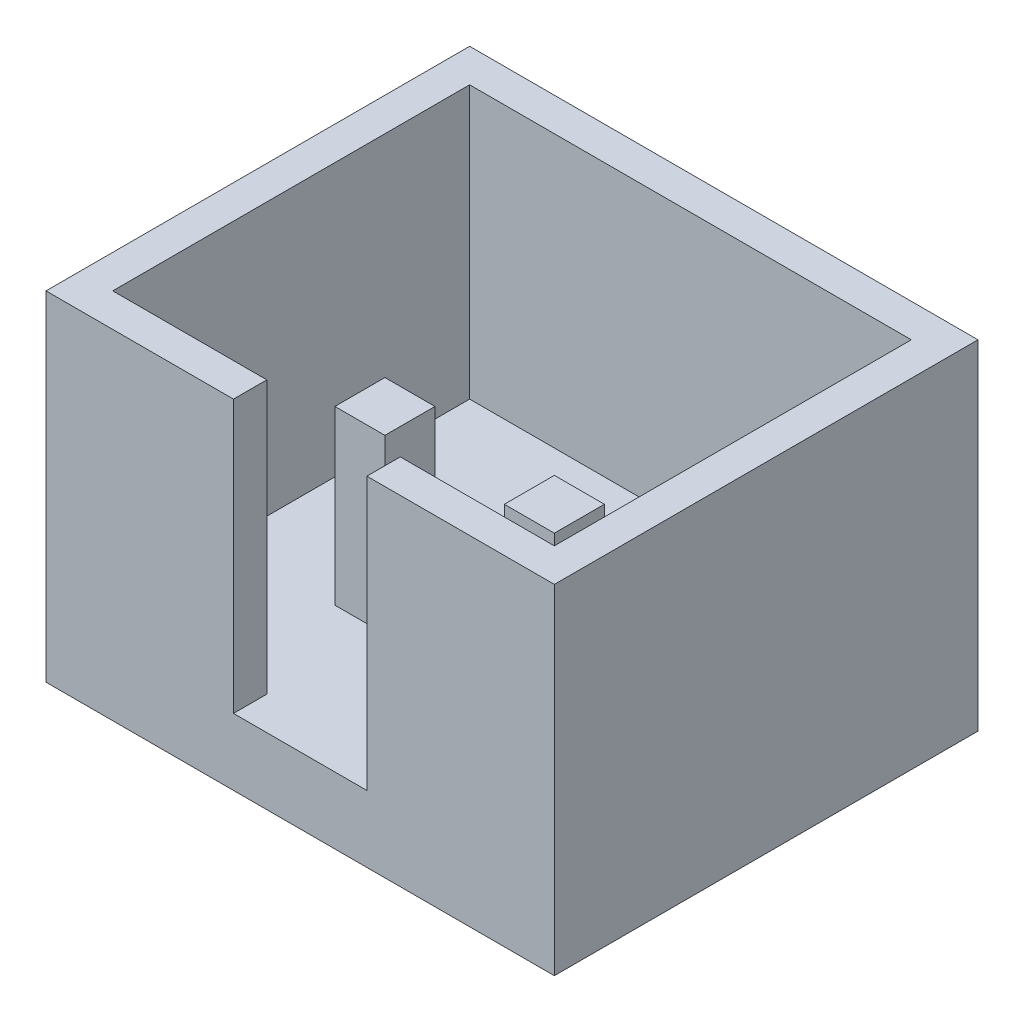
SolidWorks part; units mm, degrees
ref_plane "前视基准面" through (0, 0, 0) normal (0, 0, 1) x (1, 0, 0)
ref_plane "上视基准面" through (0, 0, 0) normal (0, 1, 0) x (1, 0, 0)
ref_plane "右视基准面" through (0, 0, 0) normal (1, 0, 0) x (0, 0, -1)
sketch "草图1" plane through (0, 0, 0) normal (0, 1, 0) x (1, 0, 0)
  line L0 (0, 7.1914) -> (0, -5.4429) construction
  line L1 (-3.81, 3.175) -> (3.81, 3.175)
  line L2 (-3.81, 3.175) -> (-3.81, -3.175)
  line L3 (-3.81, -3.175) -> (3.81, -3.175)
  line L4 (3.81, 3.175) -> (3.81, -3.175)
  line L5 (-10.6234, 0) -> (16.1963, 0) construction
  dimension "D1" = 7.62
  dimension "D2" = 6.35
extrude "拉伸1" add sketch "草图1" along normal blind 5.08
sketch "草图2" plane through (0, 5.08, 0) normal (0, 1, 0) x (-1, 0, 0)
  line L8 (3.31, -2.675) -> (3.31, 2.675)
  line L9 (3.31, 2.675) -> (-3.31, 2.675)
  line L10 (-3.31, 2.675) -> (-3.31, -2.675)
  line L11 (-3.31, -2.675) -> (3.31, -2.675)
  line L12 (3.31, -2.675) -> (3.31, 2.675)
  line L13 (3.31, 2.675) -> (-3.31, 2.675)
  line L14 (-3.31, 2.675) -> (-3.31, -2.675)
  line L15 (-3.31, -2.675) -> (3.31, -2.675)
  dimension "D1" = 0.5
extrude "切除-拉伸1" cut sketch "草图2" against normal offset from surface (4.08 mm away) 1 up to face at (0, 0, 0)
sketch "草图3" plane through (0, 0, 3.175) normal (0, 0, 1) x (1, 0, 0)
  line L0 (-3.81, 5.08) -> (3.81, 5.08) construction
  line L1 (-1, 5.08) -> (1, 5.08)
  line L2 (-1, 5.08) -> (-1, 1)
  line L3 (-1, 1) -> (1, 1)
  line L4 (1, 5.08) -> (1, 1)
  line L5 (3.31, 1) -> (-3.31, 1) construction
  line L6 (0, -1.5083) -> (0, 12.2426) construction
  dimension "D1" = 2
extrude "切除-拉伸2" cut sketch "草图3" against normal blind 1
sketch "草图4" plane through (0, 0, 0) normal (0, -1, 0) x (1, 0, 0)
  line L0 (7.6775, 0.635) -> (-8.5467, 0.635) construction
  line L2 (0, -3.6953) -> (0, 4.0669) construction
  line L3 (-1.27, 2.1009) -> (-1.27, -0.7012) construction
  line L4 (-1.645, 1.01) -> (-0.895, 1.01)
  line L5 (-1.645, 1.01) -> (-1.645, 0.26)
  line L6 (-1.645, 0.26) -> (-0.895, 0.26)
  line L7 (-0.895, 1.01) -> (-0.895, 0.26)
  line L8 (0.895, 1.01) -> (1.645, 1.01)
  line L9 (0.895, 1.01) -> (0.895, 0.26)
  line L10 (0.895, 0.26) -> (1.645, 0.26)
  line L11 (1.645, 1.01) -> (1.645, 0.26)
  dimension "D2" = 0.75
  dimension "D3" = 0.75
  dimension "D4" = 1.27
extrude "拉伸2" add sketch "草图4" along normal blind 2 and the other way offset from surface 1.5 other way up to face at (0, 5.08, 0.975)
